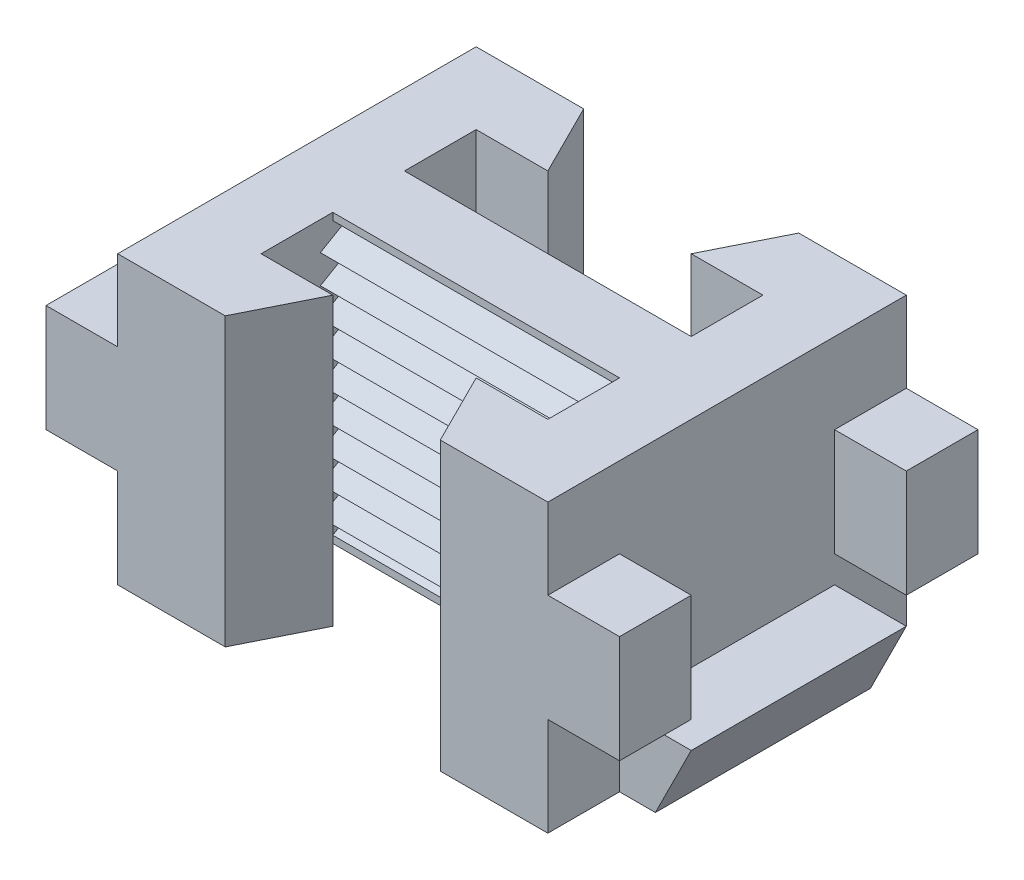
SolidWorks part; units mm, degrees
ref_plane "Front Plane" through (0, 0, 0) normal (0, 0, 1) x (1, 0, 0)
ref_plane "Top Plane" through (0, 0, 0) normal (0, 1, 0) x (1, 0, 0)
ref_plane "Right Plane" through (0, 0, 0) normal (1, 0, 0) x (0, 0, -1)
sketch "Sketch1" plane through (0, 0, 0) normal (0, 0, 1) x (1, 0, 0)
  line L1 (-7.5, -3.75) -> (-7.5, -6.25)
  line L2 (-7.5, -6.25) -> (7.5, -6.25)
  line L3 (7.5, -6.25) -> (7.5, -3.75)
  line L5 (-7.5, -3.75) -> (-7.5, 3.75)
  line L6 (-7.5, 3.75) -> (7.5, 3.75)
  line L7 (7.5, 3.75) -> (7.5, -3.75)
  line L8 (-7.5, -3.75) -> (7.5, 3.75) construction
  line L9 (7.5, -3.75) -> (-7.5, 3.75) construction
  point P0 (7.5, -3.8617)
  point P5 (-5.577, -4.471)
  point P8 (-5.2083, 4.7534)
  point P13 (0, 0)
  point P15 (0, 0)
  dimension "D5" = 2.5
  dimension "D6" = 7.5
  dimension "D7" = 15
extrude "Boss-Extrude1" add sketch "Sketch1" along normal blind 1.25 and the other way blind 1.25
sketch "Sketch4" plane through (0, 0, 0) normal (1, 0, 0) x (0, 0, -1)
  line L0 (-0.817, 3.25) -> (-1.683, 2.75) construction
  line L1 (-1.683, 2.75) -> (-1.683, 3.75) construction
  line L2 (-1.683, 3.75) -> (-0.817, 3.25) construction
  line L3 (-1.683, 3.25) -> (-0.817, 3.25) construction
  line L5 (-1.25, -6.25) -> (-1.25, 3.75) construction
  line L6 (1.25, 3.75) -> (-1.25, 3.75) construction
  line L7 (-0.817, 3.25) -> (-1.4665, 3.625)
  line L8 (-1.4665, 3.625) -> (-1.4665, 2.875)
  line L9 (-1.4665, 2.875) -> (-0.817, 3.25)
  line L10 (-1.4665, 1.875) -> (-0.817, 2.25)
  line L11 (-0.817, 2.25) -> (-1.4665, 2.625)
  line L12 (-1.4665, 2.625) -> (-1.4665, 1.875)
  line L13 (-1.4665, 0.875) -> (-0.817, 1.25)
  line L14 (-0.817, 1.25) -> (-1.4665, 1.625)
  line L15 (-1.4665, 1.625) -> (-1.4665, 0.875)
  line L16 (-1.4665, -0.125) -> (-0.817, 0.25)
  line L17 (-0.817, 0.25) -> (-1.4665, 0.625)
  line L18 (-1.4665, 0.625) -> (-1.4665, -0.125)
  line L19 (-1.4665, -1.125) -> (-0.817, -0.75)
  line L20 (-0.817, -0.75) -> (-1.4665, -0.375)
  line L21 (-1.4665, -0.375) -> (-1.4665, -1.125)
  line L22 (-1.4665, -2.125) -> (-0.817, -1.75)
  line L23 (-0.817, -1.75) -> (-1.4665, -1.375)
  line L24 (-1.4665, -1.375) -> (-1.4665, -2.125)
  line L25 (-1.4665, -3.125) -> (-0.817, -2.75)
  line L26 (-0.817, -2.75) -> (-1.4665, -2.375)
  line L27 (-1.4665, -2.375) -> (-1.4665, -3.125)
  line L28 (-1.4665, -4.125) -> (-0.817, -3.75)
  line L29 (-0.817, -3.75) -> (-1.4665, -3.375)
  line L30 (-1.4665, -3.375) -> (-1.4665, -4.125)
  line L31 (-1.4665, -5.125) -> (-0.817, -4.75)
  line L32 (-0.817, -4.75) -> (-1.4665, -4.375)
  line L33 (-1.4665, -4.375) -> (-1.4665, -5.125)
  line L34 (-1.4665, -6.125) -> (-0.817, -5.75)
  line L35 (-0.817, -5.75) -> (-1.4665, -5.375)
  line L36 (-1.4665, -5.375) -> (-1.4665, -6.125)
  line L37 (-1.4665, 2.875) -> (-1.4665, 1.875) construction
  line L38 (0, -1.4323) -> (0, 1.4323) construction
  line L39 (1.4665, 2.875) -> (1.4665, 1.875) construction
  line L40 (1.683, 3.25) -> (0.817, 3.25) construction
  line L41 (1.683, 3.75) -> (0.817, 3.25) construction
  line L42 (1.683, 2.75) -> (1.683, 3.75) construction
  line L43 (0.817, 3.25) -> (1.683, 2.75) construction
  line L44 (1.4665, -5.375) -> (1.4665, -6.125)
  line L45 (0.817, -5.75) -> (1.4665, -5.375)
  line L46 (1.4665, -6.125) -> (0.817, -5.75)
  line L47 (1.4665, -4.375) -> (1.4665, -5.125)
  line L48 (0.817, -4.75) -> (1.4665, -4.375)
  line L49 (1.4665, -5.125) -> (0.817, -4.75)
  line L50 (1.4665, -3.375) -> (1.4665, -4.125)
  line L51 (0.817, -3.75) -> (1.4665, -3.375)
  line L52 (1.4665, -4.125) -> (0.817, -3.75)
  line L53 (1.4665, -2.375) -> (1.4665, -3.125)
  line L54 (0.817, -2.75) -> (1.4665, -2.375)
  line L55 (1.4665, -3.125) -> (0.817, -2.75)
  line L56 (1.4665, -1.375) -> (1.4665, -2.125)
  line L57 (0.817, -1.75) -> (1.4665, -1.375)
  line L58 (1.4665, -2.125) -> (0.817, -1.75)
  line L59 (1.4665, -0.375) -> (1.4665, -1.125)
  line L60 (0.817, -0.75) -> (1.4665, -0.375)
  line L61 (1.4665, -1.125) -> (0.817, -0.75)
  line L62 (1.4665, 0.625) -> (1.4665, -0.125)
  line L63 (0.817, 0.25) -> (1.4665, 0.625)
  line L64 (1.4665, -0.125) -> (0.817, 0.25)
  line L65 (1.4665, 1.625) -> (1.4665, 0.875)
  line L66 (0.817, 1.25) -> (1.4665, 1.625)
  line L67 (1.4665, 0.875) -> (0.817, 1.25)
  line L68 (1.4665, 2.625) -> (1.4665, 1.875)
  line L69 (0.817, 2.25) -> (1.4665, 2.625)
  line L70 (1.4665, 1.875) -> (0.817, 2.25)
  line L71 (1.4665, 2.875) -> (0.817, 3.25)
  line L72 (1.4665, 3.625) -> (1.4665, 2.875)
  line L73 (0.817, 3.25) -> (1.4665, 3.625)
  point P6 (-1.25, 3.25)
  point P44 (0, 0)
  point P78 (1.25, 3.25)
  dimension "D1" = 1
  dimension "D2" = 1
  dimension "D3" = 0.75
  dimension "D4" = 1
  dimension "D5" = 10
extrude "Cut-Extrude1" cut sketch "Sketch4" against normal through all both and the other way through all
sketch "Sketch5" plane through (0, 0, 0) normal (1, 0, 0) x (0, 0, -1)
  line L0 (0.817, 3.25) -> (0.817, 2.25) construction
  line L1 (0.817, 2.25) -> (1.683, 2.75) construction
  line L2 (1.683, 2.75) -> (0.817, 3.25) construction
  line L3 (1.683, 2.75) -> (1.0335, 3.125)
  line L4 (1.0335, 3.125) -> (1.0335, 2.375)
  line L5 (1.0335, 2.375) -> (1.683, 2.75)
  line L6 (1.0335, 1.375) -> (1.683, 1.75)
  line L7 (1.683, 1.75) -> (1.0335, 2.125)
  line L8 (1.0335, 2.125) -> (1.0335, 1.375)
  line L9 (1.0335, 0.375) -> (1.683, 0.75)
  line L10 (1.683, 0.75) -> (1.0335, 1.125)
  line L11 (1.0335, 1.125) -> (1.0335, 0.375)
  line L12 (1.0335, -0.625) -> (1.683, -0.25)
  line L13 (1.683, -0.25) -> (1.0335, 0.125)
  line L14 (1.0335, 0.125) -> (1.0335, -0.625)
  line L15 (1.0335, -1.625) -> (1.683, -1.25)
  line L16 (1.683, -1.25) -> (1.0335, -0.875)
  line L17 (1.0335, -0.875) -> (1.0335, -1.625)
  line L18 (1.0335, -2.625) -> (1.683, -2.25)
  line L19 (1.683, -2.25) -> (1.0335, -1.875)
  line L20 (1.0335, -1.875) -> (1.0335, -2.625)
  line L21 (1.0335, -3.625) -> (1.683, -3.25)
  line L22 (1.683, -3.25) -> (1.0335, -2.875)
  line L23 (1.0335, -2.875) -> (1.0335, -3.625)
  line L24 (1.0335, -4.625) -> (1.683, -4.25)
  line L25 (1.683, -4.25) -> (1.0335, -3.875)
  line L26 (1.0335, -3.875) -> (1.0335, -4.625)
  line L27 (1.0335, -5.625) -> (1.683, -5.25)
  line L28 (1.683, -5.25) -> (1.0335, -4.875)
  line L29 (1.0335, -4.875) -> (1.0335, -5.625)
  line L30 (1.0335, 2.375) -> (1.0335, 1.375) construction
  line L31 (0, -3.9908) -> (0, 3.9908) construction
  line L32 (-1.0335, 2.375) -> (-1.0335, 1.375) construction
  line L33 (-1.683, 2.75) -> (-0.817, 3.25) construction
  line L34 (-0.817, 2.25) -> (-1.683, 2.75) construction
  line L35 (-0.817, 3.25) -> (-0.817, 2.25) construction
  line L36 (-1.0335, -4.875) -> (-1.0335, -5.625)
  line L37 (-1.683, -5.25) -> (-1.0335, -4.875)
  line L38 (-1.0335, -5.625) -> (-1.683, -5.25)
  line L39 (-1.0335, -3.875) -> (-1.0335, -4.625)
  line L40 (-1.683, -4.25) -> (-1.0335, -3.875)
  line L41 (-1.0335, -4.625) -> (-1.683, -4.25)
  line L42 (-1.0335, -2.875) -> (-1.0335, -3.625)
  line L43 (-1.683, -3.25) -> (-1.0335, -2.875)
  line L44 (-1.0335, -3.625) -> (-1.683, -3.25)
  line L45 (-1.0335, -1.875) -> (-1.0335, -2.625)
  line L46 (-1.683, -2.25) -> (-1.0335, -1.875)
  line L47 (-1.0335, -2.625) -> (-1.683, -2.25)
  line L48 (-1.0335, -0.875) -> (-1.0335, -1.625)
  line L49 (-1.683, -1.25) -> (-1.0335, -0.875)
  line L50 (-1.0335, -1.625) -> (-1.683, -1.25)
  line L51 (-1.0335, 0.125) -> (-1.0335, -0.625)
  line L52 (-1.683, -0.25) -> (-1.0335, 0.125)
  line L53 (-1.0335, -0.625) -> (-1.683, -0.25)
  line L54 (-1.0335, 1.125) -> (-1.0335, 0.375)
  line L55 (-1.683, 0.75) -> (-1.0335, 1.125)
  line L56 (-1.0335, 0.375) -> (-1.683, 0.75)
  line L57 (-1.0335, 2.125) -> (-1.0335, 1.375)
  line L58 (-1.683, 1.75) -> (-1.0335, 2.125)
  line L59 (-1.0335, 1.375) -> (-1.683, 1.75)
  line L60 (-1.0335, 2.375) -> (-1.683, 2.75)
  line L61 (-1.0335, 3.125) -> (-1.0335, 2.375)
  line L62 (-1.683, 2.75) -> (-1.0335, 3.125)
  point P37 (0, 0)
  dimension "D1" = 1
  dimension "D2" = 1
  dimension "D3" = 0.75
  dimension "D4" = 1
extrude "Boss-Extrude4" add sketch "Sketch5" along normal blind 5 and the other way blind 5
sketch "Sketch2" plane through (0, 0, 0) normal (0, 1, 0) x (1, 0, 0)
  line L1 (-7.5, -6.25) -> (-3.75, -6.25)
  line L2 (-3.75, -6.25) -> (-2.5, -3.75)
  line L3 (-2.5, -3.75) -> (-5, -3.75)
  line L7 (7.5, -6.25) -> (3.75, -6.25)
  line L8 (3.75, -6.25) -> (2.5, -3.75)
  line L9 (2.5, -3.75) -> (5, -3.75)
  line L13 (-5, -3.75) -> (-5, 3.75)
  line L14 (-5, 3.75) -> (-2.5, 3.75)
  line L15 (-2.5, 3.75) -> (-3.75, 6.25)
  line L16 (-3.75, 6.25) -> (-7.5, 6.25)
  line L17 (-7.5, 6.25) -> (-7.5, -6.25)
  line L18 (5, -3.75) -> (5, 3.75)
  line L19 (5, 3.75) -> (2.5, 3.75)
  line L20 (2.5, 3.75) -> (3.75, 6.25)
  line L21 (3.75, 6.25) -> (7.5, 6.25)
  line L22 (7.5, 6.25) -> (7.5, -6.25)
  line L23 (-5, -3.75) -> (5, 3.75) construction
  line L24 (5, -3.75) -> (-5, 3.75) construction
  point P2 (0, 0)
  point P11 (-4.6, 3.7547)
  point P12 (-4.5867, 3.75)
  point P15 (-4.0312, -3.4506)
  point P18 (-4.0478, 3.9981)
  point P19 (4.1142, -3.9815)
  point P21 (4.1308, 3.3677)
  point P23 (0, 0)
  point P25 (0, 0)
  dimension "D1" = 7.5
  dimension "D2" = 1.25
  dimension "D3" = 2.5
  dimension "D4" = 2.5
  dimension "D5" = 2.5
  dimension "D6" = 2.5
  dimension "D7" = 2.5
  dimension "D8" = 1.25
  dimension "D9" = 2.5
  dimension "D10" = 1.25
  dimension "D11" = 2.5
  dimension "D12" = 2.5
  dimension "D13" = 2.5
  dimension "D14" = 2.5
  dimension "D15" = 1.25
  dimension "D16" = 15
extrude "Boss-Extrude2" add sketch "Sketch2" along normal blind 3.75 and the other way blind 6.25
sketch "Sketch3" plane through (0, 0, 0) normal (0, 0, 1) x (1, 0, 0)
  line L0 (-6.25, -6.25) -> (-8.75, -6.25)
  line L1 (-7.5, -6.25) -> (-3.75, -6.25) construction
  line L2 (-8.75, -6.25) -> (-10, -3.75)
  line L3 (-10, -3.75) -> (-6.25, -3.75)
  line L4 (-6.25, -3.75) -> (-6.25, -6.25)
  line L5 (6.25, -6.25) -> (8.75, -6.25)
  line L6 (3.75, -6.25) -> (7.5, -6.25) construction
  line L7 (8.75, -6.25) -> (10, -3.75)
  line L8 (10, -3.75) -> (6.25, -3.75)
  line L9 (6.25, -3.75) -> (6.25, -6.25)
  line L10 (-7.5, -6.25) -> (-7.5, 3.75) construction
  line L11 (7.5, -6.25) -> (7.5, 3.75) construction
  dimension "D1" = 1.25
  dimension "D2" = 1.25
  dimension "D3" = 2.5
  dimension "D4" = 2.5
  dimension "D5" = 3.75
  dimension "D6" = 2.5
  dimension "D7" = 2.5
  dimension "D8" = 3.75
extrude "Boss-Extrude3" add sketch "Sketch3" along normal blind 3.75 and the other way blind 3.75
sketch "Sketch6" plane through (0, 0, 0) normal (0, 1, 0) x (1, 0, 0)
  line L1 (-7.5, -3.75) -> (-10, -3.75)
  line L2 (-7.5, -3.75) -> (-7.5, -6.25)
  line L3 (-7.5, -6.25) -> (-10, -6.25)
  line L4 (-10, -3.75) -> (-10, -6.25)
  line L5 (-7.5, 3.75) -> (-10, 3.75)
  line L6 (-7.5, 3.75) -> (-7.5, 6.25)
  line L7 (-7.5, 6.25) -> (-10, 6.25)
  line L8 (-10, 3.75) -> (-10, 6.25)
  line L9 (7.5, 3.75) -> (10, 3.75)
  line L10 (7.5, 3.75) -> (7.5, 6.25)
  line L11 (7.5, 6.25) -> (10, 6.25)
  line L12 (10, 3.75) -> (10, 6.25)
  line L13 (7.5, -3.75) -> (10, -3.75)
  line L14 (7.5, -3.75) -> (7.5, -6.25)
  line L15 (7.5, -6.25) -> (10, -6.25)
  line L16 (10, -3.75) -> (10, -6.25)
  dimension "D1" = 2.5
extrude "Boss-Extrude5" add sketch "Sketch6" along normal blind 0.9375 and the other way blind 2.8125
